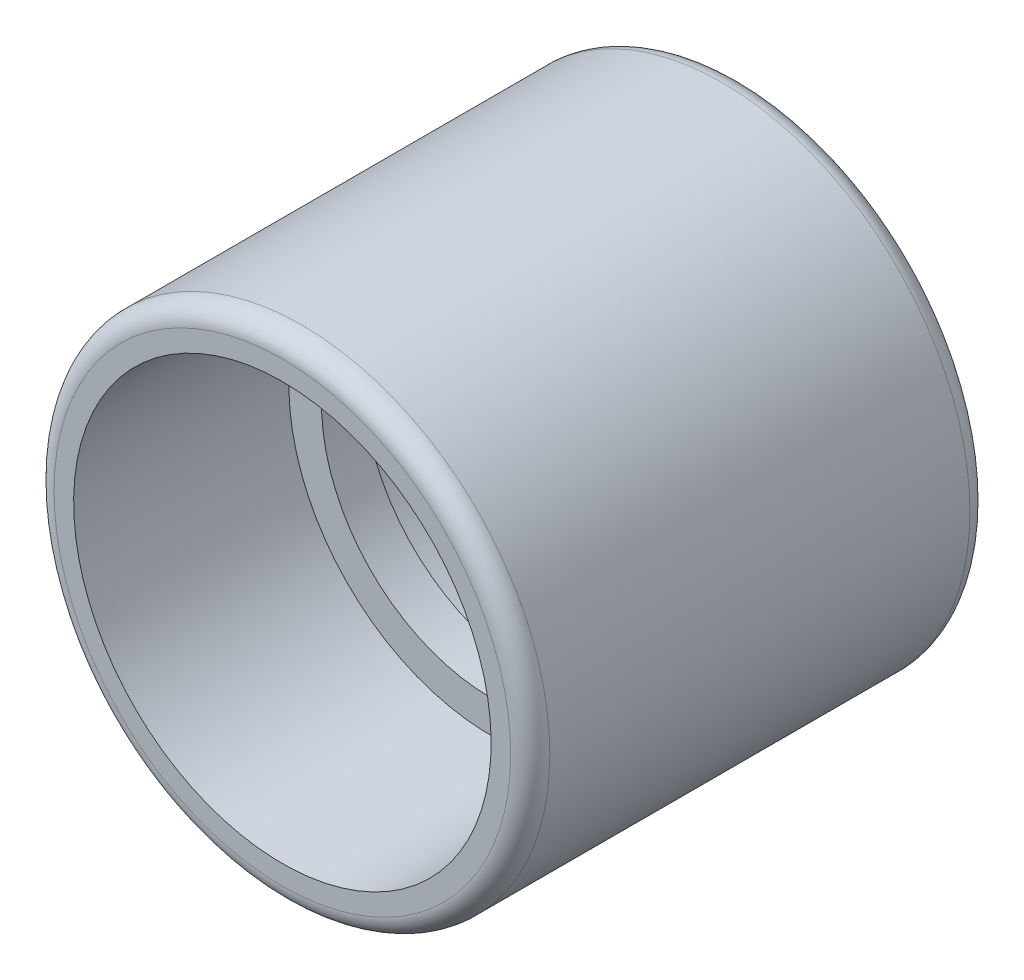
SolidWorks part; units mm, degrees
note: '?' marks a value the reader was unsure of.
material "PE Высокой плотности"
ref_plane "Front" through (0, 0, 0) normal (0, 0, 1) x (1, 0, 0)
ref_plane "Top" through (0, 0, 0) normal (0, 1, 0) x (1, 0, 0)
ref_plane "Right" through (0, 0, 0) normal (1, 0, 0) x (0, 0, -1)
sketch "BodySch" plane through (0, 0, 0) normal (0, 0, 1) x (1, 0, 0)
  circle A0 centre (0, 0) radius 9.5
  dimension "Dia" = 19
extrude "Body" add sketch "BodySch" along normal mid plane 17.6
sketch "FlowSch" plane through (0, 0, -8.8) normal (0, 0, 1) x (1, 0, 0)
  circle A0 centre (0, 0) radius 6.5
  dimension "Dia" = 13
extrude "Flow" cut sketch "FlowSch" along normal up to surface (17.6 mm away) up to face at (9.5, 0, 8.8)
sketch "ThreadSch" plane through (0, 0, 0) normal (1, 0, 0) x (0, 0, -1)
  line L0 (0, 0) -> (-8.8, 0) construction
  line L1 (-8.8, 0) -> (8.8, 0) construction
  line L2 (-0.8, 0) -> (-0.8, 7.7509)
  line L3 (-0.8, 7.7509) -> (-8.8, 8)
  line L4 (-8.8, 8) -> (-8.8, 0)
  line L5 (-8.8, 0) -> (-0.8, 0)
  line L6 (-8.8, 9.5) -> (-8.8, -9.5) construction
  dimension "D1" = 1.783
  dimension "Dia" = 16
  dimension "L1L3" = 8
revolve "Thread" cut sketch "ThreadSch" angle 360 about L0
fillet "Fillet1" radius 0.75 2 edges at (9.5, 0, -8.8) (9.5, 0, 8.8)
mirror "Mirror1" about plane through (0, 0, 0) normal (0, 0, 1) of "Thread"
sketch "Sketch1" plane through (0, 0, 0) normal (1, 0, 0) x (0, 0, -1)
  line L0 (-8.05, 0) -> (8.05, 0) construction
  line L1 (0.8, -7.7509) -> (0.8, 7.7509) construction
  line L2 (-0.8, 7.7509) -> (-0.8, -7.7509) construction
  point P0 (0, 0)
  point P1 (-0.8, 0)
  point P3 (0.8, 0)
other "CPoint1" parameters "Diameter"=16, "StubLength"=0
ref_axis "Axis1" through (0, 0, -10.8) along (0, 0, 1)?
other "CPoint2" parameters "Diameter"=16, "StubLength"=0
ref_axis "Axis2" through (0, 0, 10.8) along (0, 0, -1)?
other "RPoint1"
equation "\"EdgeRadius@Fillet1\" =  ( \"Dia@ThreadSch\" - \"Dia@FlowSch\" )  / 4"
